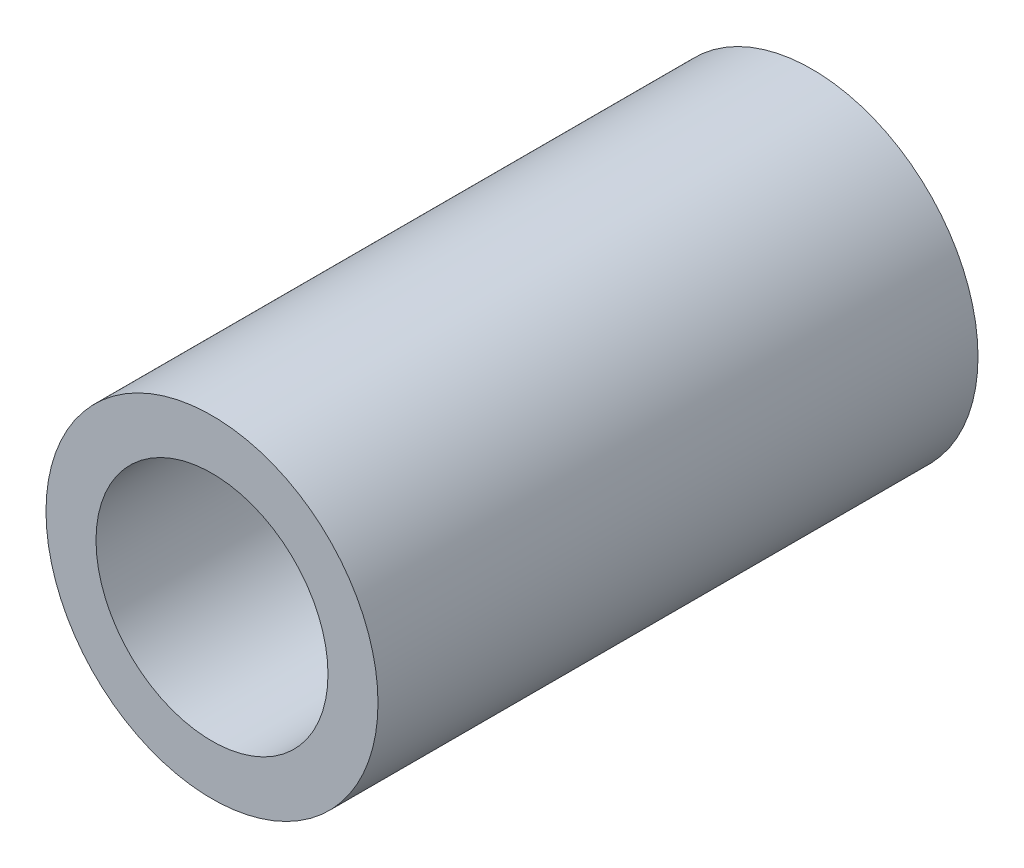
SolidWorks part; units mm, degrees
ref_plane "Front Plane" through (0, 0, 0) normal (0, 0, 1) x (1, 0, 0)
ref_plane "Top Plane" through (0, 0, 0) normal (0, 1, 0) x (1, 0, 0)
ref_plane "Right Plane" through (0, 0, 0) normal (1, 0, 0) x (0, 0, -1)
sketch "Sketch1" plane through (0, 0, 0) normal (0, 0, 1) x (1, 0, 0)
  circle A0 centre (0, 0) radius 7.366
  circle A1 centre (0, 0) radius 10.541
  dimension "D1" = 14.732
  dimension "D2" = 3.175
extrude "Boss-Extrude1" add sketch "Sketch1" along normal blind 38.1
ref_axis "Center_Axis" through (0, 0, 64.6274) along (0, 0, -1)
